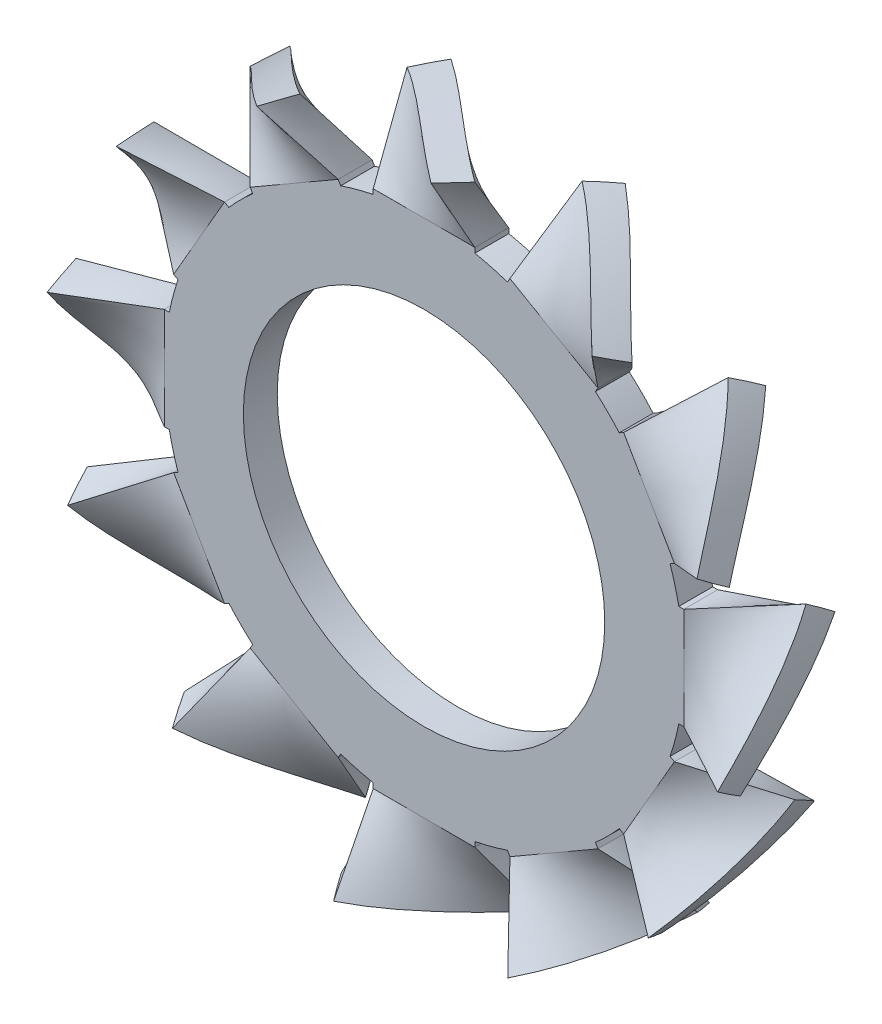
SolidWorks part; units mm, degrees
ref_plane "Front Plane" through (0, 0, 0) normal (0, 0, 1) x (1, 0, 0)
ref_plane "Top Plane" through (0, 0, 0) normal (0, 1, 0) x (1, 0, 0)
ref_plane "Right Plane" through (0, 0, 0) normal (1, 0, 0) x (0, 0, -1)
sketch "Sketch1" plane through (0, 0, 0) normal (0, 0, 1) x (1, 0, 0)
  line L0 (0, 0) -> (0, 3) construction
  line L1 (1.6, 0) -> (3, 0) construction
  circle A0 centre (0, 0) radius 1.6 construction
  circle A1 centre (0, 0) radius 3 construction
  circle A2 centre (0, 0) radius 2.3 construction
  point P4 (0, 1.6)
  point P9 (2.3, 0)
  point P10 (0, 2.3)
  point P11 (0, -2.3)
  dimension "OD" = 6
  dimension "ID" = 3.2
sketch "Sketch8" plane through (0, 0, 0) normal (1, 0, 0) x (0, 0, -1)
  line L0 (-0.2266, 2.9357) -> (-0.0734, 3.0643) construction
  line L2 (0.15, -3) -> (-0.15, -3) construction
  line L3 (0.15, -3) -> (0.15, 3) construction
  line L4 (0.15, 3) -> (-0.15, 3) construction
  line L5 (-0.15, -3) -> (-0.15, 3) construction
  line L6 (0.15, -3) -> (-0.15, 3) construction
  line L7 (0.15, 3) -> (-0.15, -3) construction
  point P0 (0, 3)
  point P5 (0, 0)
  point P7 (0.15, 0)
  point P11 (-0.15, 3)
  dimension "Thickness Range" = 0.3
  dimension "Material Thickness" = 0.2
  dimension "D1" = 40
ref_plane "Plane1" through (0, 2.3, 0) normal (0, 1, 0) x (-1, 0, 0)
sketch "Sketch2" plane through (0, 2.3, 0) normal (0, 1, 0) x (-1, 0, 0)
  line L0 (-0.45, 0) -> (0.45, 0) construction
  line L1 (-0.45, 0.15) -> (0.45, 0.15)
  line L2 (-0.45, 0.15) -> (-0.45, -0.15)
  line L3 (-0.45, -0.15) -> (0.45, -0.15)
  line L4 (0.45, 0.15) -> (0.45, -0.15)
  dimension "D1" = 0.9
ref_plane "Plane2" through (0, 3, 0) normal (0, 1, 0) x (-1, 0, 0)
sketch "Sketch3" plane through (0, 3, 0) normal (0, 1, 0) x (-1, 0, 0)
  line L0 (0, 0) -> (0.5171, -0.4339) construction
  line L1 (0.6039, -0.3305) -> (0.4303, -0.5373)
  line L2 (0.6039, -0.3305) -> (-0.4303, 0.5373)
  line L3 (0.4303, -0.5373) -> (-0.6039, 0.3305)
  line L4 (-0.4303, 0.5373) -> (-0.6039, 0.3305)
  line L5 (2.3, 0) -> (-2.3, 0) construction
  line L6 (0, 0) -> (0.0868, 0.1034) construction
  dimension "D1" = 40
  dimension "D2" = 0.27
  dimension "D3" = 1.35
loft "Loft1" add profiles "Sketch3", "Sketch2" connector at (0.4303, 3, 0.5373) connector at (0.45, 2.3, 0.15)
sketch "Sketch4" plane through (0, 2.3, 0) normal (0, -1, 0) x (1, 0, 0)
  line L4 (0.45, -0.15) -> (0.45, 0.15)
  line L5 (0.45, 0.15) -> (-0.45, 0.15)
  line L6 (-0.45, 0.15) -> (-0.45, -0.15)
  line L7 (-0.45, -0.15) -> (0.45, -0.15)
  line L8 (0.45, -0.15) -> (0.45, 0.15)
  line L9 (0.45, 0.15) -> (-0.45, 0.15)
  line L10 (-0.45, 0.15) -> (-0.45, -0.15)
  line L11 (-0.45, -0.15) -> (0.45, -0.15)
  dimension "D1" = 0
extrude "Extrude1" add sketch "Sketch4" along normal up to vertex (0.7 mm away) up to point (0, 1.6, 0)
ref_axis "Axis1" through (0, 0, -0.5721) along (0, 0, 1)
pattern_circular "CirPattern1" count 12 over 360 about axis through (0, 0, -0.5721) along (0, 0, 1) of bodies 102
sketch "Sketch5" plane through (0, 0, 0) normal (0, 0, 1) x (1, 0, 0)
  circle A0 centre (0, 0) radius 2.3 construction
  circle A1 centre (0, 0) radius 1.6 construction
  circle A2 centre (0, 0) radius 2.3
  circle A3 centre (0, 0) radius 1.6
extrude "Extrude2" add sketch "Sketch5" along normal up to vertex (0.15 mm away) and the other way up to vertex (0.15 mm away) up to point (-0.45, 1.6, 0.15) other way up to point (-0.45, 1.6, -0.15)
sketch "Sketch6" plane through (0, 0, 0) normal (0, 0, 1) x (1, 0, 0)
  circle A0 centre (0, 0) radius 3 construction
  circle A1 centre (0, 0) radius 3
extrude "Cut-Extrude1" cut sketch "Sketch6" against normal through all and the other way through all flip side to cut
sketch "Sketch7" plane through (0, 0, 0) normal (1, 0, 0) x (0, 0, -1)
  line L0 (0.15, -2.3) -> (-0.15, -2.3) construction
  line L1 (0.15, -1.6) -> (0.15, 1.6) construction
ref_axis "Axis2" through (0, 0, 0.15) along (0, 0, -1)
ref_plane "Plane3" through (0, 0, 0.5201) normal (0, 0, 1) x (1, 0, 0)
ref_plane "Plane4" through (0, 0, -0.5201) normal (0, 0, -1) x (-1, 0, 0)
equation "\"D1@Sketch2\"=\"Thickness Range@Sketch8\" * 3"
equation "\"D2@Sketch3\" = \"Thickness Range@Sketch8\" * 0.9"
equation "\"D3@Sketch3\" = \"D2@Sketch3\" * 5"
